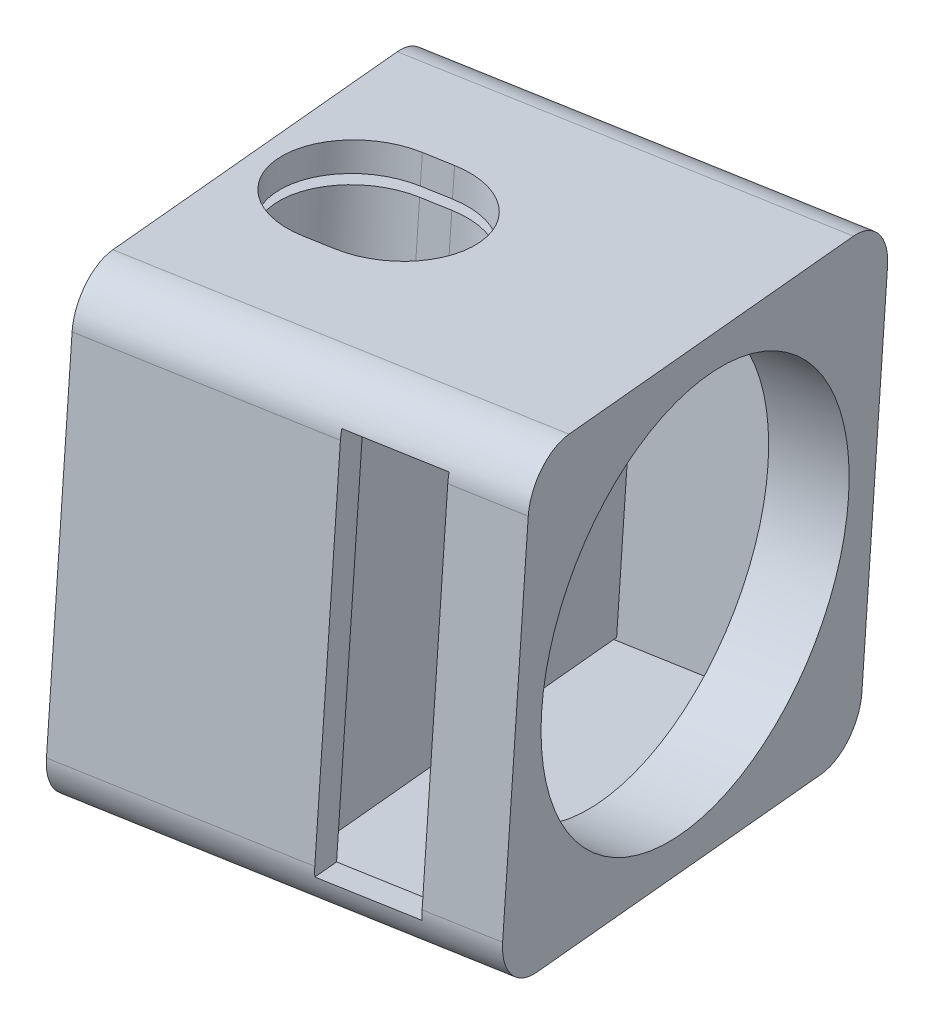
SolidWorks part; units mm, degrees
material "ABS"
ref_plane "Front Plane" through (0, 0, 0) normal (0, 0, 1) x (1, 0, 0)
ref_plane "Top Plane" through (0, 0, 0) normal (0, 1, 0) x (1, 0, 0)
ref_plane "Right Plane" through (0, 0, 0) normal (1, 0, 0) x (0, 0, -1)
sketch "Sketch1" plane through (37.19, 0, -6.5576) normal (0.9848, 0, -0.1736) x (-0.1736, 0, -0.9848)
  line L1 (-16.5317, 5.2115) -> (-17.3934, -4.3498)
  line L2 (-17.3934, -4.3498) -> (-7.8322, -5.2115)
  line L3 (-7.8322, -5.2115) -> (-6.9704, 4.3498)
  line L4 (-6.9704, 4.3498) -> (-16.5317, 5.2115)
  line L5 (-16.5248, -3.6248) -> (-8.5571, -4.3429)
  line L6 (-8.5571, -4.3429) -> (-7.839, 3.6248)
  line L7 (-7.839, 3.6248) -> (-15.8067, 4.3429)
  line L8 (-15.8067, 4.3429) -> (-16.5248, -3.6248)
  line L9 (-16.5248, -3.6248) -> (-8.5571, -4.3429) construction
  line L10 (-8.5571, -4.3429) -> (-7.839, 3.6248) construction
  line L11 (-7.839, 3.6248) -> (-15.8067, 4.3429) construction
  line L12 (-15.8067, 4.3429) -> (-16.5248, -3.6248) construction
  line L13 (-7.6219, 3.806) -> (-15.9879, 4.5601)
  line L14 (-15.9879, 4.5601) -> (-16.742, -3.806)
  line L15 (-16.742, -3.806) -> (-8.3759, -4.5601)
  line L16 (-8.3759, -4.5601) -> (-7.6219, 3.806)
  circle A1 centre (-12.1819, 0) radius 3.9
  circle A2 centre (-12.1819, 0) radius 3.9 construction
  circle A3 centre (-12.1819, 0) radius 4.1
  circle M10 centre (-12.1819, 0) radius 3.9
  line M11 (-16.5248, -3.6248) -> (-8.5571, -4.3429)
  line M12 (-8.5571, -4.3429) -> (-7.839, 3.6248)
  line M13 (-7.839, 3.6248) -> (-15.8067, 4.3429)
  line M14 (-15.8067, 4.3429) -> (-16.5248, -3.6248)
  dimension "D4" = 0.2
  dimension "D1" = 0
  dimension "D2" = 0
  dimension "D3" = 0.8
  dimension "D5" = 0.2
extrude "Boss-Extrude1" add sketch "Sketch1" along normal blind 1.5 contours L1 L2 L3 L4 | A3
extrude "Boss-Extrude2" add sketch "Sketch1<3>" against normal blind 7 contours L3 L4 L1 L2 L16 L15 L14 L13 region at (39.2329, 4.6338, 5.0279)
sketch "Sketch1<3>" plane through (37.19, 0, -6.5576) normal (0.9848, 0, -0.1736) x (-0.1736, 0, -0.9848) same geometry as "Sketch1"
extrude "Boss-Extrude3" add sketch "Sketch1<4>" along normal blind 4.5 from surface separate body contours A3 M12 M13 | M10 | A3 M11 M12 | A3 M13 M14 | A3 M12 M13 M14 M11 M10 | A3 M14 M11 region at (39.9057, -2.8852, 8.8435) region at (39.8367, -2.5535, 8.4522) region at (38.8044, -3.4568, 2.5979) region at (39.8064, 3.4568, 8.2806) region at (38.7051, 2.8852, 2.035) region at (39.3054, 0, 5.4392) starting at face at (32.4118, 0, 6.6548)
sketch "Sketch1<4>" plane through (37.19, 0, -6.5576) normal (0.9848, 0, -0.1736) x (-0.1736, 0, -0.9848) same geometry as "Sketch1"
sketch "Sketch2" plane through (-0.0578, 3.6915, -0.3277) normal (-0.0156, 0.996, -0.0884) x (0.9999, 0.0156, -0.0007)
  line L0 (32.4032, -6.6063) -> (40.7741, -5.1303) construction
  line L1 (37.3358, -5.7865) -> (8719.7447, -49246.1742) construction
  line L2 (34.3728, -6.259) -> (34.9637, -6.1549) construction
  line L3 (34.095, -4.6833) -> (34.6859, -4.5792)
  line L4 (39.9406, -0.4033) -> (31.5697, -1.8793)
  line L5 (31.5697, -1.8793) -> (33.2367, -11.3334)
  line L6 (33.2367, -11.3334) -> (41.6076, -9.8574)
  line L7 (41.6076, -9.8574) -> (39.9406, -0.4033)
  line L8 (39.9406, -0.4033) -> (31.5697, -1.8793)
  line L9 (31.5697, -1.8793) -> (33.2367, -11.3334)
  line L10 (33.2367, -11.3334) -> (41.6076, -9.8574)
  line L11 (41.6076, -9.8574) -> (39.9406, -0.4033)
  line L12 (34.6507, -7.8347) -> (35.2416, -7.7305)
  arc A0 (34.095, -4.6833) -> (34.6507, -7.8347) centre (34.3728, -6.259) ccw
  arc A1 (35.2416, -7.7305) -> (34.6859, -4.5792) centre (34.9637, -6.1549) ccw
  point P10 (34.6683, -6.2069)
  point P15 (32.7971, -6.5369)
  point P16 (36.5394, -5.877)
  point P17 (37.031, -5.8403)
  point P18 (32.6175, -6.6185)
  dimension "D2" = 5
  dimension "D3" = 3.2
  dimension "D4" = 0.4
  dimension "D5" = 0.8
  dimension "D1" = 0
extrude "Cut-Extrude1" cut sketch "Sketch2" against normal through all contours L12 A1 L3 A0 region at (34.602, 4.7806, 5.8311)
fillet "Fillet1" radius 1 4 edges at (35.8419, -5.2115, 1.6331) (35.6922, 4.3498, 0.7844) (37.5022, -4.3498, 11.0491) (37.3525, 5.2115, 10.2004)
sketch "Sketch3" plane through (2.7901, 1.4481, 15.8235) normal (0.1729, 0.0898, 0.9808) x (0.9849, -0.0158, -0.1722)
  line L4 (35.7133, 3.4721) -> (35.8399, -4.5269)
  line L5 (35.8399, -4.5269) -> (37.8396, -4.4952)
  line L6 (37.8396, -4.4952) -> (37.713, 3.5038)
  line L7 (37.713, 3.5038) -> (35.7133, 3.4721)
  line L8 (35.7133, 3.4721) -> (35.8399, -4.5269)
  line L9 (35.8399, -4.5269) -> (37.8396, -4.4952)
  line L10 (37.8396, -4.4952) -> (37.713, 3.5038)
  line L11 (37.713, 3.5038) -> (35.7133, 3.4721)
  dimension "D1" = 0
extrude "Cut-Extrude2" cut sketch "Sketch3" along normal through all
